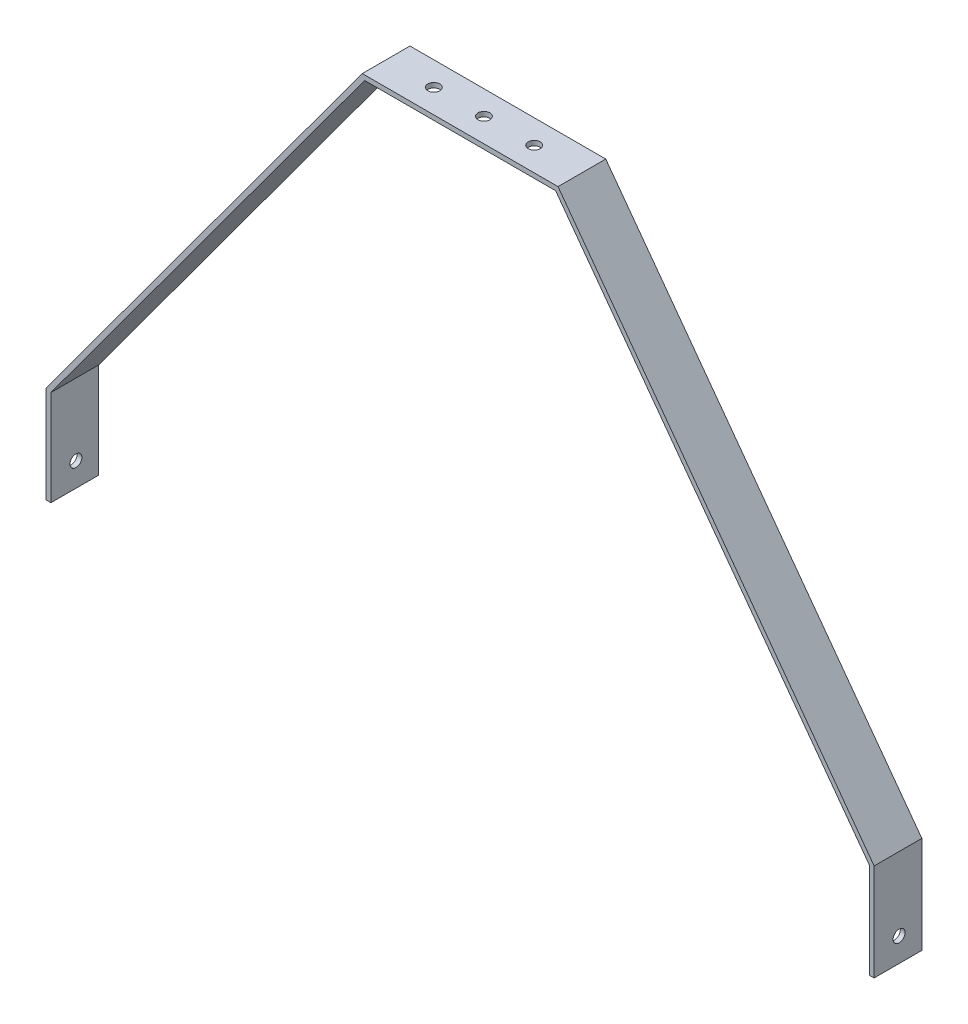
SolidWorks part; units mm, degrees
ref_plane "Front Plane" through (0, 0, 0) normal (0, 0, 1) x (1, 0, 0)
ref_plane "Top Plane" through (0, 0, 0) normal (0, 1, 0) x (1, 0, 0)
ref_plane "Right Plane" through (0, 0, 0) normal (1, 0, 0) x (0, 0, -1)
sketch "Sketch9" plane through (0, 0, 0) normal (0, 0, 1) x (1, 0, 0)
  line L0 (-158.1031, -153.4931) -> (-158.1031, -113.4931)
  line L1 (-158.1031, -113.4931) -> (-26.6761, 65.4229)
  line L2 (-26.6761, 65.4229) -> (53.3239, 65.4229)
  line L3 (53.3239, 65.4229) -> (184.7508, -113.4931)
  line L4 (184.7508, -113.4931) -> (184.7508, -153.4931)
  line L5 (184.7508, -153.4931) -> (186.7508, -153.4931)
  line L6 (186.7508, -153.4931) -> (186.7508, -112.8375)
  line L7 (186.7508, -112.8375) -> (54.3363, 67.4229)
  line L8 (54.3363, 67.4229) -> (-27.6886, 67.4229)
  line L9 (-27.6886, 67.4229) -> (-160.1031, -112.8375)
  line L10 (-160.1031, -112.8375) -> (-160.1031, -153.4931)
  line L11 (-160.1031, -153.4931) -> (-158.1031, -153.4931)
  dimension "D1" = 40
  dimension "D2" = 222
  dimension "D3" = 80
  dimension "D4" = 222
  dimension "D5" = 40
  dimension "D6" = 126.3
  dimension "D7" = 143.7
  dimension "D8" = 143.7
  dimension "D9" = 2
  dimension "D10" = 2
  dimension "D11" = 2
  dimension "D12" = 2
  dimension "D13" = 2
extrude "Boss-Extrude1" add sketch "Sketch9" along normal blind 20
sketch "Sketch10" plane through (186.7508, 0, 0) normal (1, 0, 0) x (0, 0, -1)
  line L1 (-20, -153.4931) -> (0, -153.4931) construction
  circle A0 centre (-9.5346, -143.4931) radius 2.5
  dimension "D1" = 5
  dimension "D2" = 10
extrude "Cut-Extrude1" cut sketch "Sketch10" against normal blind 479 and the other way blind 90
sketch "Sketch11" plane through (0, 67.4229, 0) normal (0, 1, 0) x (1, 0, 0)
  line L0 (54.3363, 0) -> (-27.6886, 0) construction
  line L1 (-27.6886, -20) -> (-27.6886, 0) construction
  line L2 (54.3363, -20) -> (54.3363, 0) construction
  circle A0 centre (-7.6886, -10) radius 2.5
  circle A1 centre (34.3363, -10) radius 2.5
  circle A2 centre (13.3114, -10) radius 2.5
  point P6 (-27.6886, -10)
  point P11 (54.3363, -10)
  point P14 (13.3239, 0)
  dimension "D3" = 5
  dimension "D4" = 5
  dimension "D8" = 5
  dimension "D1" = 10
  dimension "D2" = 20
  dimension "D5" = 20
  dimension "D6" = 10
  dimension "D7" = 21
  dimension "D9" = 10
extrude "Cut-Extrude2" cut sketch "Sketch11" against normal blind 47 and the other way blind 47
